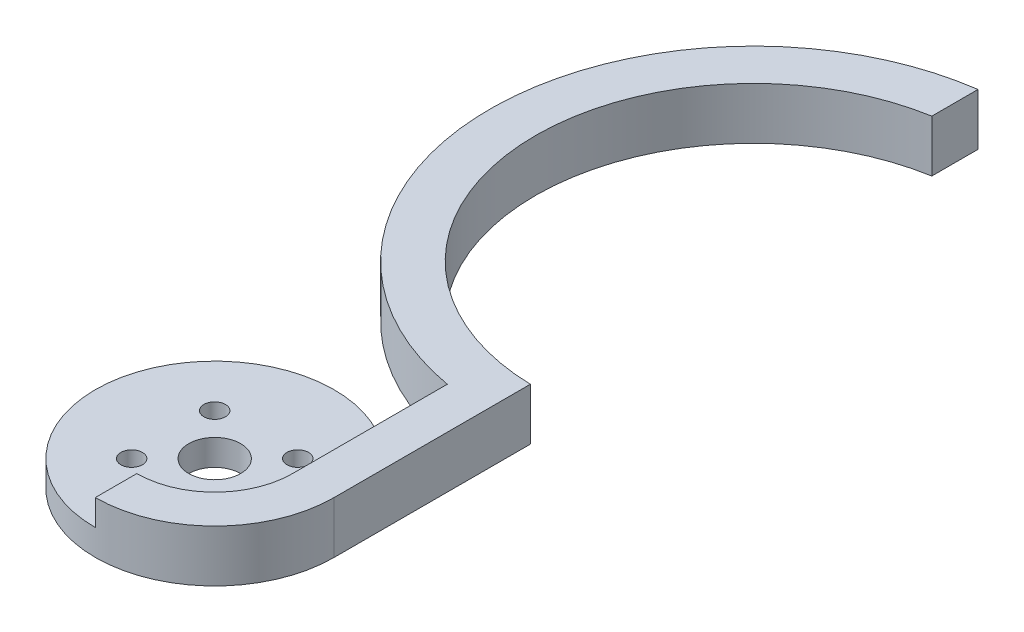
SolidWorks part; units mm, degrees
ref_plane "Front Plane" through (0, 0, 0) normal (0, 0, 1) x (1, 0, 0)
ref_plane "Top Plane" through (0, 0, 0) normal (0, 1, 0) x (1, 0, 0)
ref_plane "Right Plane" through (0, 0, 0) normal (1, 0, 0) x (0, 0, -1)
sketch "Sketch1" plane through (0, 0, 0) normal (0, 1, 0) x (1, 0, 0)
  line L1 (23, 29) -> (24, 29)
  line L2 (23, 0) -> (23, 23)
  line L4 (15, 23) -> (0, 23)
  line L6 (23, 23) -> (23, 0)
  line L9 (24, 37.8) -> (24, 79.8)
  line L13 (23, 23) -> (23, 29)
  line L20 (15, 23) -> (15, 29.8036)
  line L21 (24, 79.8) -> (24, 143.1)
  line L22 (23, 29) -> (23, 29.0098)
  line L23 (15, 23) -> (15, 0)
  line L24 (0, -15) -> (0, -23)
  line L25 (16.9372, 91.363) -> (16.9372, 154.663)
  line L26 (23, 29.0098) -> (23, 37.8119)
  arc A0 (0, 23) -> (0, -23) centre (0, 0) ccw
  circle A1 centre (-8, 8) radius 2.075
  circle A2 centre (-8, -8) radius 2.075
  circle A3 centre (8, 8) radius 2.075
  circle A4 centre (8, -8) radius 2.075
  circle A5 centre (0, 0) radius 5
  arc A6 (15, 17.4356) -> (23, 0) centre (0, 0) ccw
  arc A7 (23, 29.0098) -> (15, 29.8036) centre (24, 79.8) ccw
  arc A8 (23, 37.8119) -> (16.9372, 38.3981) centre (24, 79.8) ccw
  circle A9 centre (0, 0) radius 15
  arc A10 (16.9372, 38.3981) -> (24, 37.8) centre (24, 79.8) ccw
  dimension "D1" = 46
  dimension "D7" = 4.15
  dimension "D8" = 4.15
  dimension "D9" = 4.15
  dimension "D10" = 4.15
  dimension "D4" = 10
  dimension "D11" = 84
  dimension "D2" = 8
  dimension "D3" = 6
  dimension "D5" = 1
  dimension "D6" = 50.8
  dimension "D12" = 63.3
extrude "Boss-Extrude1" add sketch "Sketch1" along normal blind 5 contours L4 A0 L2 L13 L20 A4 A3 A2 A1 | L20 L2 L13 | A6 region at (21.39, 0, -26) region at (-22.4033, 0, 0) region at (-10.3066, 0, -10.3066)
extrude "Boss-Extrude2" add sketch "Sketch1<3>" along normal blind 10 contours A9 L24 A6 L2 L13 L22 A7 L21 A8 L20 L23 region at (21.39, 0, -26)
sketch "Sketch1<3>" plane through (0, 0, 0) normal (0, 1, 0) x (1, 0, 0) same geometry as "Sketch1"
equation "\"stem length\"= 6"
equation "\"D3@Sketch1\"=\"stem length\""
equation "\"circle radius\" = 34"
equation "\"curve thickness\" = 16"
equation "\"D11@Sketch1\"=\"circle radius\" * 2 + \"curve thickness\""
equation "\"D2@Sketch1\"=\"curve thickness\" / 2"
equation "\"height thickness\"= 10"
equation "\"D1@Boss-Extrude2\"=\"height thickness\""
